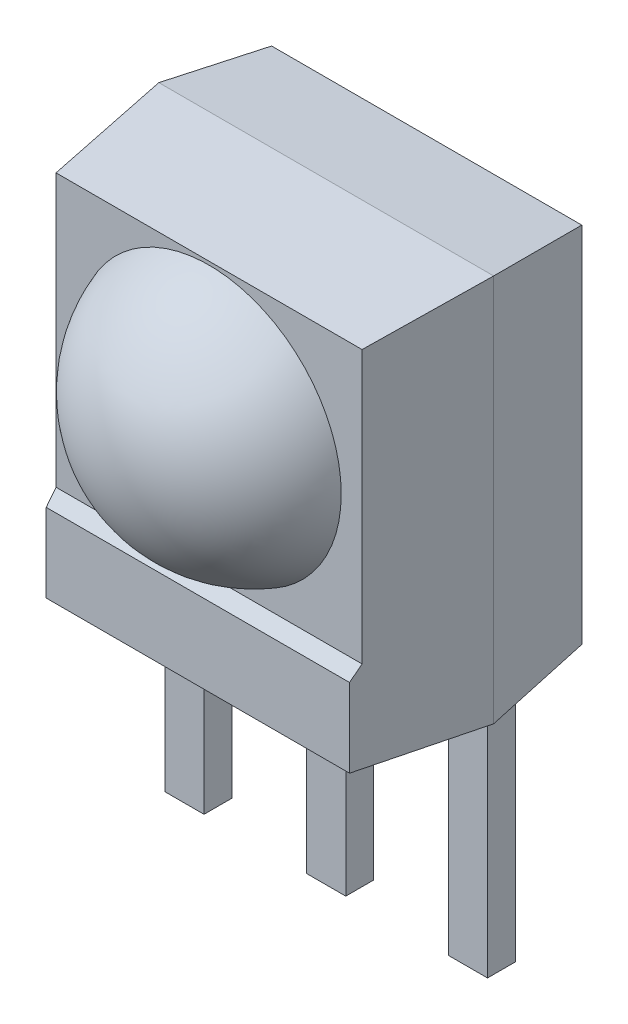
SolidWorks part; units mm, degrees
ref_plane "Plan de face" through (0, 0, 0) normal (0, 0, 1) x (1, 0, 0)
ref_plane "Plan de dessus" through (0, 0, 0) normal (0, 1, 0) x (1, 0, 0)
ref_plane "Plan de droite" through (0, 0, 0) normal (1, 0, 0) x (0, 0, -1)
sketch "Esquisse1" plane through (0, 0, 0) normal (1, 0, 0) x (0, 0, -1)
  line L0 (0, 6.95) -> (1.8, 6.729)
  line L1 (-2.1, 6.95) -> (1.8, 6.95) construction
  line L2 (-2.1, 0) -> (-2.1, 0.221) construction
  line L3 (-2.1, 0) -> (1.8, 0) construction
  line L4 (1.8, 6.95) -> (1.8, 0) construction
  line L5 (0, 0) -> (0, 6.95) construction
  line L6 (0, 6.95) -> (-2.1, 6.729)
  line L7 (1.8, 6.729) -> (-2.1, 6.729) construction
  line L8 (0, 0) -> (1.8, 0.221)
  line L9 (0, 0) -> (-2.1, 0.221)
  line L10 (-2.1, 0.221) -> (1.8, 0.221) construction
  line L11 (1.8, 6.729) -> (1.8, 0.221)
  line L12 (-2.1, 6.729) -> (-2.1, 1.85)
  line L13 (-2.1, 6.95) -> (-2.1, 6.729) construction
  line L14 (-2.1, 1.85) -> (-2.3, 1.65)
  line L15 (-2.3, 1.65) -> (-2.3, 0.2421)
  line L16 (-2.1, 1.85) -> (-2.1, 0.221) construction
  line L18 (-2.1, 0.221) -> (-2.3, 0.2421)
  dimension "D1" = 3.9
  dimension "D2" = 6.95
  dimension "D3" = 1.8
  dimension "D4" = 4.1
  dimension "D5" = 5.3
  dimension "D6" = 45
  dimension "D7" = 7
extrude "Boss.-Extru.1" add sketch "Esquisse1" along normal mid plane 6
sketch "Esquisse2" plane through (0, 0, 0) normal (0, 1, 0) x (1, 0, 0)
  line L0 (-3, 0) -> (-2.779, 1.8)
  line L1 (3, 1.8) -> (-3, 1.8) construction
  line L2 (-3, 0) -> (-2.7176, -2.3)
  line L4 (3, -2.3) -> (-3, -2.3) construction
  line L5 (-3, 1.8) -> (-3, 0) construction
  line L6 (-3, 0) -> (-3, -2.1) construction
  dimension "D1" = 7
  dimension "D2" = 7
extrude "Enlèv. mat.-Extru.4" cut sketch "Esquisse2" against normal through all and the other way through all flip side to cut
ref_plane "Plan1" through (0, 4.3, 0) normal (0, 1, 0) x (-1, 0, 0)
ref_axis "Axe1" through (0, 4.3, -2.005) along (0, 0, 1)
sketch "Esquisse3" plane through (0, 4.3, 0) normal (0, 1, 0) x (-1, 0, 0)
  line L0 (0, 2.1) -> (2.3685, 2.1)
  line L1 (0, -2.005) -> (0, 2.505) construction
  line L2 (-3, 2.1) -> (2.7422, 2.1) construction
  line L3 (-3, 2.1) -> (2.7422, 2.1) construction
  line L4 (0, 2.1) -> (0, 3.8)
  line L5 (-3, -1.8) -> (2.779, -1.8) construction
  arc A0 (2.3685, 2.1) -> (0, 3.8) centre (0, 1.3) ccw
  dimension "D1" = 2.5
  dimension "D2" = 5.6
revolve "Révolution1" add sketch "Esquisse3" angle 360 about L4
mirror "Symétrie1" about plane through (0, 0, 0) normal (1, 0, 0) of "Enlèv. mat.-Extru.4"
sketch "Esquisse4" plane through (0, 0, 0) normal (0, 1, 0) x (1, 0, 0)
  line L0 (3, 0) -> (-3, 0) construction
  line L1 (-0.35, 0.5) -> (0.35, 0.5)
  line L2 (-0.35, 0.5) -> (-0.35, 0)
  line L3 (-0.35, 0) -> (0.35, 0)
  line L4 (0.35, 0.5) -> (0.35, 0)
  line L6 (2.19, 0.5) -> (2.89, 0.5)
  line L7 (2.19, 0.5) -> (2.19, 0)
  line L8 (2.19, 0) -> (2.89, 0)
  line L9 (2.89, 0.5) -> (2.89, 0)
  line L10 (-2.89, 0.5) -> (-2.19, 0.5)
  line L11 (-2.89, 0.5) -> (-2.89, 0)
  line L12 (-2.89, 0) -> (-2.19, 0)
  line L13 (-2.19, 0.5) -> (-2.19, 0)
  line L14 (0, 2.005) -> (0, -2.505) construction
  point P11 (2.54, 0)
  point P18 (-2.54, 0)
  dimension "D1" = 0.7
  dimension "D2" = 0.5
  dimension "D3" = 2.54
  dimension "D4" = 2.54
extrude "Boss.-Extru.2" add sketch "Esquisse4" along normal up to next and the other way blind 4
